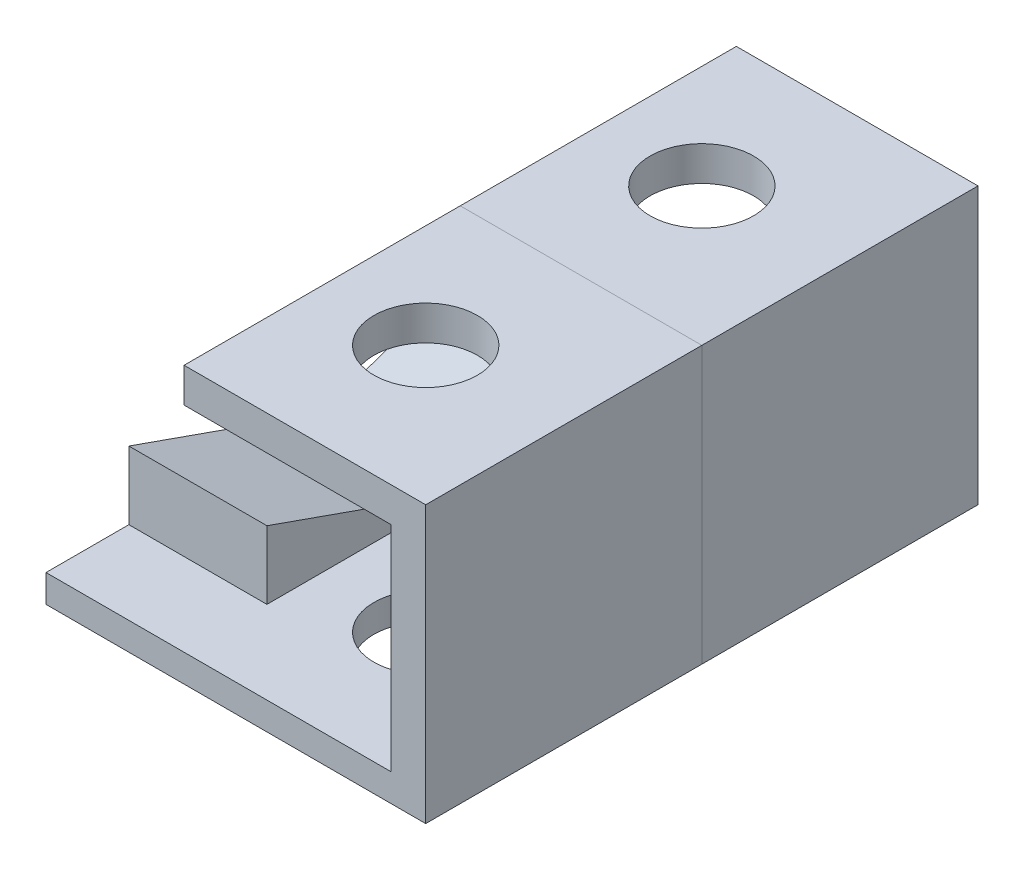
SolidWorks part; units mm, degrees
ref_plane "Front Plane" through (0, 0, 0) normal (0, 0, 1) x (1, 0, 0)
ref_plane "Top Plane" through (0, 0, 0) normal (0, 1, 0) x (1, 0, 0)
ref_plane "Right Plane" through (0, 0, 0) normal (1, 0, 0) x (0, 0, -1)
sketch "Sketch1" plane through (0, 0, 0) normal (0, 1, 0) x (1, 0, 0)
  line L1 (0, 0) -> (31.75, 0)
  line L2 (0, 0) -> (0, 25.4)
  line L3 (0, 25.4) -> (31.75, 25.4)
  line L4 (31.75, 0) -> (31.75, 25.4)
  line L5 (0, 25.4) -> (12.7, 25.4)
  line L6 (0, 25.4) -> (0, 0)
  line L7 (0, 0) -> (12.7, 0)
  line L8 (12.7, 25.4) -> (12.7, 0)
  line L9 (31.75, 25.4) -> (34.925, 25.4)
  line L10 (31.75, 25.4) -> (31.75, 0)
  line L11 (31.75, 0) -> (34.925, 0)
  line L12 (34.925, 25.4) -> (34.925, 0)
  line L13 (0, 25.4) -> (12.7, 25.4)
  line L14 (0, 25.4) -> (0, 17.6554)
  line L15 (0, 17.6554) -> (12.7, 17.6554)
  line L16 (12.7, 25.4) -> (12.7, 17.6554)
  circle A0 centre (22.225, 12.7) radius 4.7625
  dimension "D4" = 3.175
  dimension "D6" = 9.525
  dimension "D1" = 31.75
  dimension "D2" = 25.4
  dimension "D3" = 12.7
  dimension "D5" = 9.525
extrude "Boss-Extrude1" add sketch "Sketch1" along normal blind 2.54 contours L3 L8 L1 L4 A0 | L6 L5 L8 L7 region at (13.0175, 0, -8.8277)
extrude "Boss-Extrude2" add sketch "Sketch1<3>" along normal blind 2.54 contours L8 L3 L2 L1 region at (6.35, 0, -8.8277)
sketch "Sketch1<3>" plane through (0, 0, 0) normal (0, 1, 0) x (1, 0, 0) same geometry as "Sketch1"
extrude "Boss-Extrude3" add sketch "Sketch1<4>" along normal blind 25.4 contours L12 L9 L4 L11 region at (33.3375, 0, -12.7)
sketch "Sketch1<4>" plane through (0, 0, 0) normal (0, 1, 0) x (1, 0, 0) same geometry as "Sketch1"
sketch "Sketch2" plane through (31.75, 0, 0) normal (-1, 0, 0) x (0, 0, 1)
  line L0 (0, 25.4) -> (0, 2.54) construction
  line L1 (-25.4, 25.4) -> (0, 25.4)
  line L2 (-25.4, 25.4) -> (-25.4, 22.225)
  line L3 (-25.4, 22.225) -> (0, 22.225)
  line L4 (0, 25.4) -> (0, 22.225)
  dimension "D1" = 3.175
extrude "Boss-Extrude4" add sketch "Sketch2" along normal blind 19.05
sketch "Sketch4" plane through (0, 25.4, 0) normal (0, 1, 0) x (1, 0, 0)
  line L0 (12.7, 0) -> (12.7, 25.4) construction
  circle A0 centre (22.225, 12.7) radius 4.7625
  circle A1 centre (22.225, 12.7) radius 4.7625 construction
  dimension "D1" = 9.525
  dimension "D2" = 0
extrude "Cut-Extrude1" cut sketch "Sketch4" against normal blind 3.175
sketch "Sketch7" plane through (0, 0, 0) normal (0, 0, 1) x (1, 0, 0)
  line L0 (31.75, 22.225) -> (34.925, 22.225)
  line L1 (34.925, 25.4) -> (34.925, 0) construction
sketch "Sketch8" plane through (0, 0, -25.4) normal (0, 0, -1) x (-1, 0, 0)
  line L0 (-31.75, 22.225) -> (-34.925, 22.225)
sketch "Sketch9" plane through (34.925, 0, 0) normal (1, 0, 0) x (0, 0, -1)
  line L0 (0, 22.225) -> (25.4, 22.225)
  line L1 (25.4, 25.4) -> (25.4, 0) construction
sketch "Sketch10" plane through (0, 25.4, 0) normal (0, 1, 0) x (1, 0, 0)
  line L0 (34.925, 0) -> (31.75, 0)
  line L1 (12.7, 0) -> (34.925, 0) construction
  line L2 (34.925, 25.4) -> (31.75, 25.4)
  line L3 (12.7, 25.4) -> (34.925, 25.4) construction
  line L4 (31.75, 25.4) -> (31.75, 0)
sketch "Sketch12" plane through (0, 2.54, 0) normal (0, 1, 0) x (1, 0, 0)
  line L0 (12.7, 0) -> (12.7, 25.4) construction
  line L1 (0, 25.4) -> (12.7, 25.4)
  line L2 (0, 25.4) -> (0, 17.7786)
  line L3 (0, 17.7786) -> (12.7, 17.7786)
  line L4 (12.7, 25.4) -> (12.7, 17.7786)
  line L6 (0, 17.7786) -> (12.7, 17.7786)
  line L7 (0, 17.7786) -> (0, 0)
  line L8 (0, 0) -> (12.7, 0)
  line L9 (12.7, 17.7786) -> (12.7, 0)
sketch "Sketch16" plane through (0, 0, 0) normal (-1, 0, 0) x (0, 0, 1)
  line L0 (-17.7786, 2.54) -> (-17.7786, 8.8051)
  line L1 (-25.4, 2.54) -> (-17.7786, 2.54) construction
  line L2 (-17.7786, 2.54) -> (0, 2.54) construction
  line L3 (-17.7786, 8.8051) -> (0, 2.54)
  line L4 (-17.7786, 2.54) -> (0, 2.54)
extrude "Boss-Extrude5" add sketch "Sketch16" against normal blind 12.7
mirror "Mirror3" about plane through (0, 2.54, 0) normal (0, 0, -1) of bodies 108
